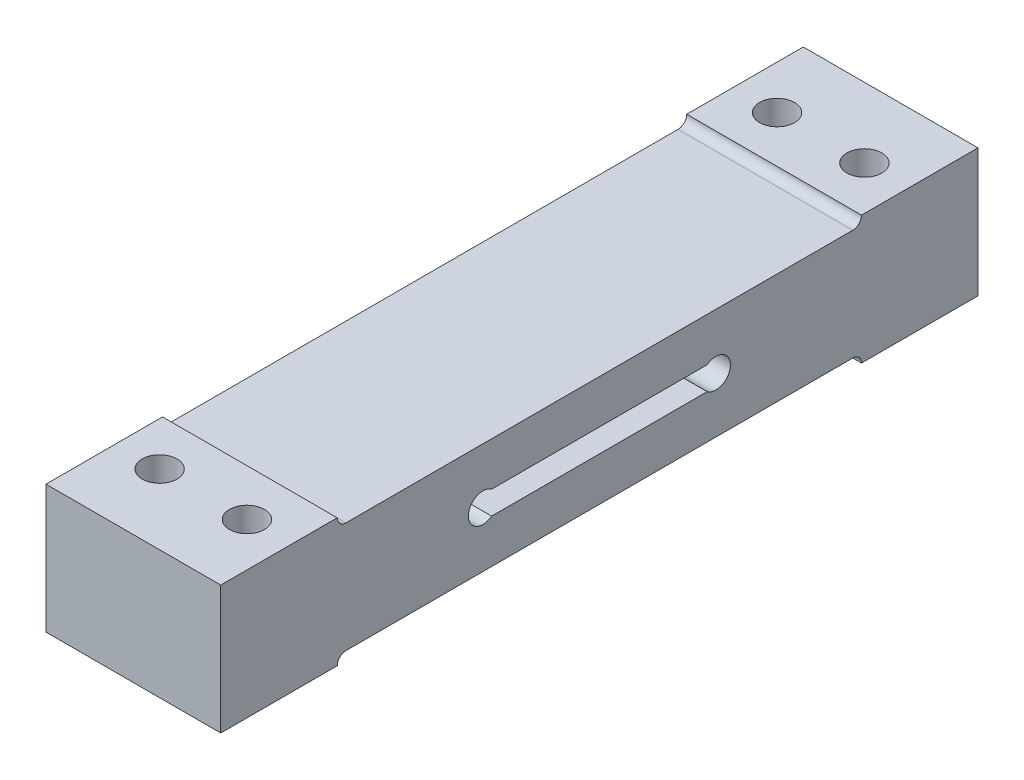
SolidWorks part; units mm, degrees
ref_plane "Front Plane" through (0, 0, 0) normal (0, 0, 1) x (1, 0, 0)
ref_plane "Top Plane" through (0, 0, 0) normal (0, 1, 0) x (1, 0, 0)
ref_plane "Right Plane" through (0, 0, 0) normal (1, 0, 0) x (0, 0, -1)
sketch "Sketch1" plane through (0, 0, 0) normal (1, 0, 0) x (0, 0, -1)
  line L1 (65, -11) -> (-65, -11)
  line L2 (65, -11) -> (65, 11)
  line L3 (65, 11) -> (-65, 11)
  line L4 (-65, -11) -> (-65, 11)
  line L5 (65, -11) -> (-65, 11) construction
  line L6 (65, 11) -> (-65, -11) construction
  line L8 (-1000, 0) -> (49000, 0) construction
  line L9 (-18.5, 2) -> (18.5, 2)
  line L10 (-18.5, -2) -> (18.5, -2)
  arc A2 (-18.5, 2) -> (-18.5, -2) centre (-20, 0) ccw
  arc A3 (18.5, -2) -> (18.5, 2) centre (20, 0) ccw
  point P0 (0, 0)
  dimension "D5" = 20
  dimension "D6" = 20
  dimension "D3" = 5
  dimension "D4" = 5
  dimension "D1" = 130
  dimension "D2" = 22
  dimension "D7" = 2
  dimension "D8" = 4
extrude "Boss-Extrude1" add sketch "Sketch1" along normal mid plane 30
sketch "Sketch2" plane through (0, 11, 0) normal (0, 1, 0) x (1, 0, 0)
  line L1 (7.5, -53) -> (-7.5, -53) construction
  line L2 (7.5, -53) -> (7.5, 53) construction
  line L3 (7.5, 53) -> (-7.5, 53) construction
  line L4 (-7.5, -53) -> (-7.5, 53) construction
  line L5 (7.5, -53) -> (-7.5, 53) construction
  line L6 (7.5, 53) -> (-7.5, -53) construction
  circle A0 centre (-7.5, 53) radius 3
  circle A1 centre (7.5, 53) radius 3
  circle A2 centre (-7.5, -53) radius 3
  circle A3 centre (7.5, -53) radius 3
  point P0 (0, 0)
  dimension "D3" = 6
  dimension "D4" = 6
  dimension "D5" = 6
  dimension "D6" = 6
  dimension "D1" = 106
  dimension "D2" = 15
extrude "Cut-Extrude1" cut sketch "Sketch2" against normal through all
sketch "Sketch3" plane through (15, 0, 0) normal (1, 0, 0) x (0, 0, -1)
  line L0 (65, 11) -> (-65, 11) construction
  line L1 (45, -11) -> (-45, -11)
  line L2 (45, -11) -> (45, -9.5)
  line L3 (45, 11) -> (-45, 11)
  line L4 (-45, -11) -> (-45, -9.5)
  line L5 (45, -11) -> (-45, 11) construction
  line L6 (45, 11) -> (-45, -11) construction
  line L7 (-45, 9.5) -> (45, 9.5)
  line L8 (-45, -9.5) -> (45, -9.5)
  line L9 (-45, 9.5) -> (-45, 11)
  line L10 (45, 9.5) -> (45, 11)
  point P0 (0, 0)
  dimension "D1" = 90
  dimension "D2" = 1.5
  dimension "D3" = 1.5
extrude "Cut-Extrude2" cut sketch "Sketch3" against normal blind 30
fillet "Fillet1" radius 1.5 4 edges at (0, -9.5, 45) (0, -9.5, -45) (0, 9.5, -45) (0, 9.5, 45)
